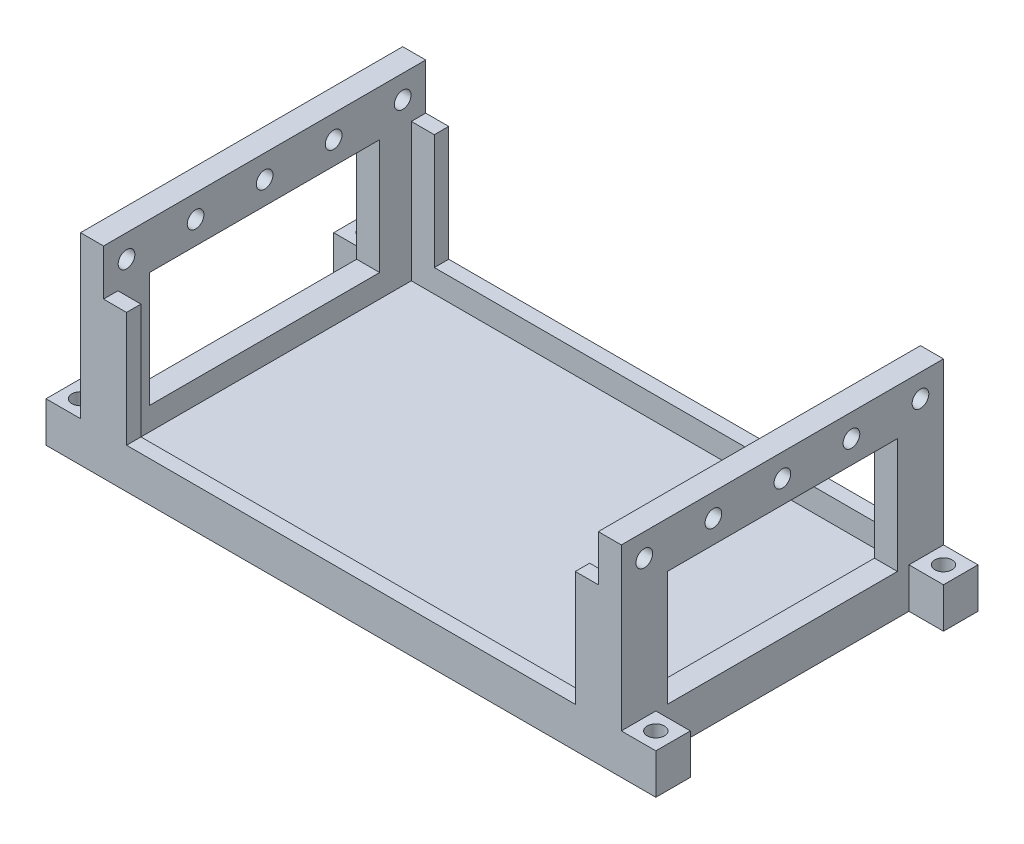
SolidWorks part; units mm, degrees
ref_plane "Front Plane" through (0, 0, 0) normal (0, 0, 1) x (1, 0, 0)
ref_plane "Top Plane" through (0, 0, 0) normal (0, 1, 0) x (1, 0, 0)
ref_plane "Right Plane" through (0, 0, 0) normal (1, 0, 0) x (0, 0, -1)
sketch "Sketch1" plane through (0, 0, 0) normal (0, 1, 0) x (1, 0, 0)
  line L0 (47, -944) -> (47, 49056) construction
  line L1 (0, 0) -> (94, 0)
  line L2 (0, 6) -> (0, 50)
  line L3 (0, 56) -> (94, 56)
  line L4 (94, 6) -> (94, 50)
  line L5 (0, 56) -> (-6, 56)
  line L7 (0, 50) -> (-6, 50)
  line L8 (-6, 56) -> (-6, 50)
  line L9 (-1000, 28) -> (49000, 28) construction
  line L10 (94, 50) -> (100, 50)
  line L11 (100, 56) -> (100, 50)
  line L12 (94, 56) -> (100, 56)
  line L14 (94, 0) -> (100, 0)
  line L15 (100, 0) -> (100, 6)
  line L16 (94, 6) -> (100, 6)
  line L18 (0, 6) -> (-6, 6)
  line L19 (-6, 0) -> (-6, 6)
  line L20 (0, 0) -> (-6, 0)
  circle A0 centre (-3, 53) radius 1.5
  circle A1 centre (97, 53) radius 1.5
  circle A2 centre (97, 3) radius 1.5
  circle A3 centre (-3, 3) radius 1.5
  point P11 (-3, 50)
  point P13 (-6, 53)
  point P17 (47, 56)
  point P18 (0, 28)
  dimension "D5" = 3
  dimension "D1" = 94
  dimension "D2" = 56
  dimension "D3" = 6
  dimension "D4" = 6
  dimension "D6" = 106
extrude "Boss-Extrude1" add sketch "Sketch1" along normal blind 3
sketch "Sketch2" plane through (0, 3, 0) normal (0, 1, 0) x (1, 0, 0)
  line L5 (4, 53.5) -> (90, 53.5)
  line L6 (4, 53.5) -> (4, 2.5)
  line L7 (4, 2.5) -> (90, 2.5)
  line L8 (0, 50) -> (0, 6)
  line L9 (-6, 0) -> (100, 0)
  line L10 (94, 6) -> (94, 50)
  line L11 (100, 56) -> (-6, 56)
  line L12 (0, 50) -> (0, 6)
  line L13 (-6, 0) -> (100, 0)
  line L14 (94, 6) -> (94, 50)
  line L15 (100, 56) -> (-6, 56)
  line L16 (90, 53.5) -> (90, 2.5)
  line L28 (100, 0) -> (100, 6)
  line L29 (100, 0) -> (100, 6)
  line L30 (100, 6) -> (94, 6)
  line L31 (100, 6) -> (94, 6)
  line L32 (94, 50) -> (100, 50)
  line L33 (94, 50) -> (100, 50)
  line L34 (100, 50) -> (100, 56)
  line L35 (100, 50) -> (100, 56)
  line L36 (-6, 56) -> (-6, 50)
  line L37 (-6, 56) -> (-6, 50)
  line L38 (-6, 50) -> (0, 50)
  line L39 (-6, 50) -> (0, 50)
  line L40 (0, 6) -> (-6, 6)
  line L41 (0, 6) -> (-6, 6)
  line L42 (-6, 6) -> (-6, 0)
  line L43 (-6, 6) -> (-6, 0)
  circle A0 centre (-3, 53) radius 1.5 construction
  circle A1 centre (-3, 53) radius 1.5
  circle A2 centre (97, 53) radius 1.5 construction
  circle A3 centre (97, 3) radius 1.5 construction
  circle A4 centre (-3, 3) radius 1.5 construction
  circle A5 centre (97, 53) radius 1.5
  circle A6 centre (97, 3) radius 1.5
  circle A7 centre (-3, 3) radius 1.5
  dimension "D2" = 2.5
  dimension "D3" = 4
  dimension "D4" = 4
  dimension "D5" = 2.5
  dimension "D1" = 0
extrude "Boss-Extrude2" add sketch "Sketch2" along normal blind 4
sketch "Sketch3" plane through (0, 7, 0) normal (0, 1, 0) x (1, 0, 0)
  line L0 (90, 53.5) -> (4, 53.5) construction
  line L1 (0, 56) -> (8, 56)
  line L2 (0, 56) -> (0, 53.5)
  line L3 (0, 53.5) -> (8, 53.5)
  line L4 (8, 56) -> (8, 53.5)
  line L5 (4, 53.5) -> (4, 2.5) construction
  line L6 (0, 53.5) -> (4, 53.5)
  line L7 (0, 53.5) -> (0, 48)
  line L8 (0, 48) -> (4, 48)
  line L9 (4, 53.5) -> (4, 48)
  line L10 (47, -946.5) -> (47, 49053.5) construction
  line L11 (100, 56) -> (-6, 56) construction
  line L12 (-996, 28) -> (49004, 28) construction
  line L13 (94, 48) -> (90, 48)
  line L14 (90, 53.5) -> (90, 48)
  line L15 (94, 53.5) -> (90, 53.5)
  line L16 (94, 53.5) -> (94, 48)
  line L17 (94, 53.5) -> (86, 53.5)
  line L18 (86, 56) -> (86, 53.5)
  line L19 (94, 56) -> (86, 56)
  line L20 (94, 56) -> (94, 53.5)
  line L21 (94, 2.5) -> (90, 2.5)
  line L22 (90, 2.5) -> (90, 8)
  line L23 (94, 8) -> (90, 8)
  line L24 (94, 2.5) -> (94, 8)
  line L25 (94, 0) -> (94, 2.5)
  line L26 (94, 0) -> (86, 0)
  line L27 (86, 0) -> (86, 2.5)
  line L28 (94, 2.5) -> (86, 2.5)
  line L29 (0, 8) -> (4, 8)
  line L30 (4, 2.5) -> (4, 8)
  line L31 (0, 2.5) -> (4, 2.5)
  line L32 (0, 2.5) -> (0, 8)
  line L33 (0, 2.5) -> (8, 2.5)
  line L34 (8, 0) -> (8, 2.5)
  line L35 (0, 0) -> (8, 0)
  line L36 (0, 0) -> (0, 2.5)
  line L37 (100, 56) -> (-6, 56) construction
  line L38 (0, 50) -> (0, 6) construction
  point P17 (47, 56)
  point P20 (4, 28)
  line M19 (100, 56) -> (-6, 56)
  line M20 (0, 50) -> (0, 6)
  line M21 (-6, 0) -> (100, 0)
  line M22 (94, 6) -> (94, 50)
  line M23 (90, 2.5) -> (4, 2.5)
  line M24 (4, 2.5) -> (4, 53.5)
  line M25 (4, 53.5) -> (90, 53.5)
  line M26 (90, 53.5) -> (90, 2.5)
  dimension "D1" = 8
  dimension "D2" = 8
extrude "Boss-Extrude3" add sketch "Sketch3" along normal blind 20 contours L8 L3 M20 M24 | L4 L3 M19 M20 M25 | L31 L29 M20 M24 | L34 L31 M21 M23 M20 | L23 L21 M22 M26 | L27 L21 M21 M22 M23 | L15 L13 M22 M26 | L18 L15 M19 M25 M22 region at (4, 7, -54.75) region at (2, 7, -50.75) region at (90, 7, -54.75) region at (92, 7, -50.75) region at (2, 7, -5.25) region at (4, 7, -1.25) region at (92, 7, -5.25) region at (90, 7, -1.25)
sketch "Sketch4" plane through (0, 27, 0) normal (0, 1, 0) x (1, 0, 0)
  line L0 (0, 0) -> (8, 0) construction
  line L1 (0, 56) -> (4, 56)
  line L2 (0, 56) -> (0, 0)
  line L3 (0, 0) -> (4, 0)
  line L4 (4, 56) -> (4, 0)
  line L5 (86, 0) -> (94, 0) construction
  line L6 (94, 56) -> (90, 56)
  line L7 (94, 56) -> (94, 0)
  line L8 (94, 0) -> (90, 0)
  line L9 (90, 56) -> (90, 0)
extrude "Boss-Extrude4" add sketch "Sketch4" along normal blind 8
sketch "Sketch5" plane through (0, 0, 0) normal (-1, 0, 0) x (0, 0, 1)
  line L0 (-48, 27) -> (-48, 35) construction
  line L2 (-56, 35) -> (0, 35) construction
  line L3 (-56, 35) -> (-56, 7) construction
  line L4 (0, 35) -> (0, 7) construction
  circle A0 centre (-52, 31) radius 1.45
  circle A1 centre (-40, 31) radius 1.45
  circle A2 centre (-28, 31) radius 1.45
  circle A3 centre (-16, 31) radius 1.45
  circle A4 centre (-4, 31) radius 1.45
  point P9 (-48, 31)
  dimension "D1" = 2.9
  dimension "D2" = 4
  dimension "D4" = 4
  dimension "D3" = 5
extrude "Cut-Extrude1" cut sketch "Sketch5" against normal through all
